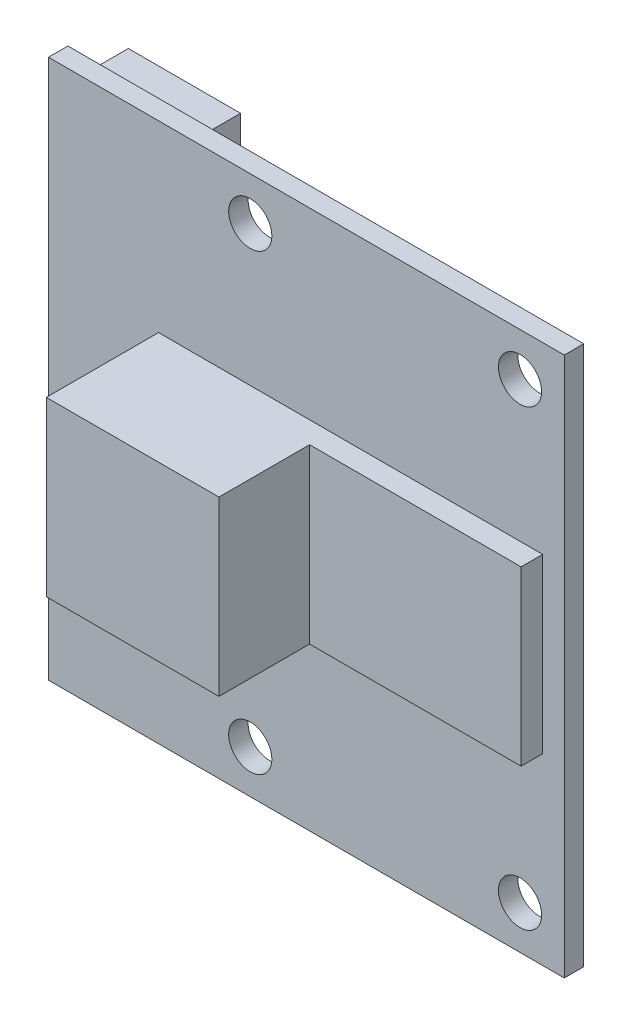
SolidWorks part; units mm, degrees
ref_plane "Alzado" through (0, 0, 0) normal (0, 0, 1) x (1, 0, 0)
ref_plane "Planta" through (0, 0, 0) normal (0, 1, 0) x (1, 0, 0)
ref_plane "Vista lateral" through (0, 0, 0) normal (1, 0, 0) x (0, 0, -1)
ref_axis "Eje1" through (-88.54, 0, 0) along (1, 0, 0)
sketch "Croquis2" plane through (0, 0, 0) normal (0, 0, 1) x (1, 0, 0)
  line L0 (-11.5, 0) -> (12.4, 0)
  line L1 (-88.54, 0) -> (89.44, 0) construction
  line L2 (12.4, 0) -> (12.4, 12.5)
  line L3 (12.4, 12.5) -> (-11.5, 12.5)
  line L4 (-11.5, 12.5) -> (-11.5, 0)
  dimension "D1" = 12.5
  dimension "D2" = 23.9
  dimension "D3" = 11.5
extrude "Saliente-Extruir1" add sketch "Croquis2" along normal blind 0.9
sketch "Croquis3" plane through (0, 0, 0.9) normal (0, 0, 1) x (1, 0, 0)
  line L0 (12.4, 12.5) -> (-11.5, 12.5) construction
  line L1 (-11.5, 12.5) -> (-11.5, 0) construction
  circle A0 centre (-2.15, 10.5) radius 1
  circle A1 centre (10.35, 10.5) radius 1
  dimension "D1" = 2
  dimension "D2" = 2
  dimension "D3" = 2
  dimension "D4" = 2
  dimension "D5" = 9.35
  dimension "D6" = 21.85
sketch "Croquis4" plane through (0, 0, 0.9) normal (0, 0, 1) x (1, 0, 0)
  line L0 (-6.4, 0) -> (-6.4, 4)
  line L1 (-11.5, 0) -> (12.4, 0) construction
  line L2 (-6.4, 4) -> (11.4, 4)
  line L3 (11.4, 4) -> (11.4, 0)
  line L4 (11.4, 0) -> (-6.4, 0)
  line L5 (-11.5, 12.5) -> (-11.5, 0) construction
  line L6 (12.4, 0) -> (12.4, 12.5) construction
  dimension "D1" = 5.1
  dimension "D2" = 4
  dimension "D3" = 1
extrude "Saliente-Extruir2" add sketch "Croquis4" along normal blind 1
sketch "Croquis5" plane through (0, 0, 1.9) normal (0, 0, 1) x (1, 0, 0)
  line L0 (11.4, 4) -> (-6.4, 4) construction
  line L1 (-6.4, 0) -> (1.6, 0)
  line L2 (-6.4, 0) -> (-6.4, 4)
  line L3 (-6.4, 4) -> (1.6, 4)
  line L4 (1.6, 0) -> (1.6, 4)
  dimension "D1" = 8
extrude "Saliente-Extruir3" add sketch "Croquis5" along normal blind 4.2
sketch "Croquis6" plane through (0, 0, 0) normal (0, 0, -1) x (-1, 0, 0)
  line L1 (11.5, 0) -> (6.3, 0)
  line L2 (11.5, 0) -> (11.5, 11)
  line L3 (11.5, 11) -> (6.3, 11)
  line L4 (6.3, 0) -> (6.3, 11)
  dimension "D1" = 5.2
  dimension "D2" = 11
extrude "Saliente-Extruir4" add sketch "Croquis6" along normal blind 2.8
hole_wizard "Diámetro de taladro Ø2.0 (2)1" positions "Croquis3D1" profile "Croquis8" hole size "Ø2.0" standard "Ansi Metric" end condition up to next
sketch3d "Croquis3D1"
  point P0 (-2.15, 10.5, 0.9)
  point P3 (10.35, 10.5, 0.9)
sketch "Croquis8" plane through (-2.15, 10.5, 0.9) normal (1, 0, 0) x (0, -1, 0)
  line L0 (0, 0) -> (0, 0.901)
  line L1 (0, 0.901) -> (1, 0.901)
  line L2 (1, 0.901) -> (1, 0)
  line L5 (1, 0) -> (0, 0)
  line L11 (0, -6.35) -> (0, 107.95) construction
  dimension "Diámetro de taladro hasta el siguiente" = 2
  dimension "Profundidad de taladro hasta el siguiente" = 0.9011
mirror "Simetría1" about plane through (0, 0, 0) normal (0, 1, 0) of "Saliente-Extruir2", "Saliente-Extruir1", "Saliente-Extruir3", "Saliente-Extruir4"
mirror "Simetría2" about plane through (0, 0, 0) normal (0, 1, 0) of "Diámetro de taladro Ø2.0 (2)1"
